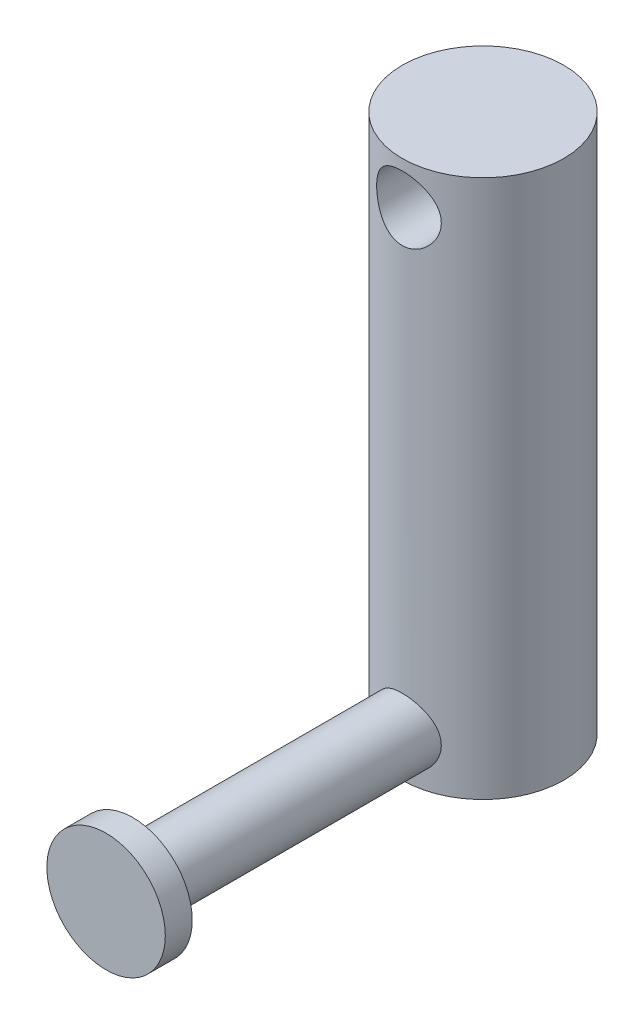
SolidWorks part; units mm, degrees
ref_plane "Front Plane" through (0, 0, 0) normal (0, 0, 1) x (1, 0, 0)
ref_plane "Top Plane" through (0, 0, 0) normal (0, 1, 0) x (1, 0, 0)
ref_plane "Right Plane" through (0, 0, 0) normal (1, 0, 0) x (0, 0, -1)
sketch "Sketch1" plane through (0, 0, 0) normal (0, 1, 0) x (1, 0, 0)
  circle A0 centre (0, 0) radius 15
  dimension "D1" = 30
extrude "Boss-Extrude1" add sketch "Sketch1" along normal blind 100
ref_plane "Plane1" through (0, 0, 15) normal (0, 0, 1) x (1, 0, 0)
sketch "Sketch2" plane through (0, 0, 15) normal (0, 0, 1) x (1, 0, 0)
  circle A0 centre (0, 8) radius 6
  dimension "D1" = 12
  dimension "D2" = 8
extrude "Boss-Extrude2" add sketch "Sketch2" along normal blind 50 and the other way up to surface separate body other way up to face at (0, 100, 15)
sketch "Sketch3" plane through (0, 0, 0) normal (0, 0, 1) x (1, 0, 0)
  line L0 (15, 100) -> (-15, 100) construction
  circle A0 centre (0, 92) radius 6
  dimension "D1" = 12
  dimension "D2" = 8
extrude "Cut-Extrude1" cut sketch "Sketch3" along normal through all both and the other way through all
sketch "Sketch4" plane through (0, 0, 65) normal (0, 0, 1) x (1, 0, 0)
  circle A0 centre (0, 8) radius 11
  circle A1 centre (0, 8) radius 6 construction
  dimension "D1" = 22
extrude "Boss-Extrude3" add sketch "Sketch4" along normal blind 5
